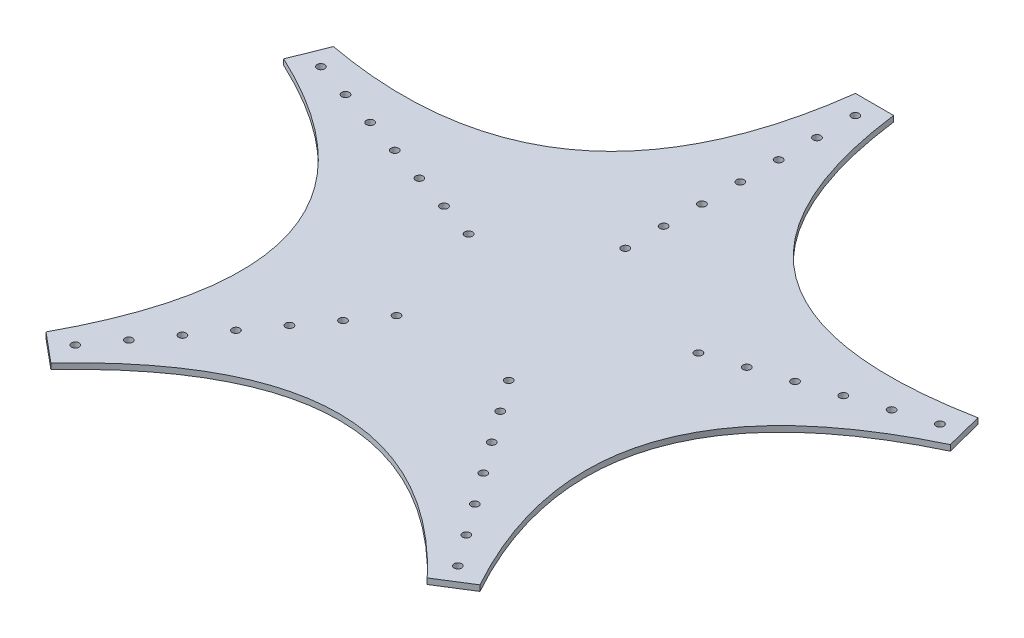
SolidWorks part; units mm, degrees
ref_plane "Front Plane" through (0, 0, 0) normal (0, 0, 1) x (1, 0, 0)
ref_plane "Top Plane" through (0, 0, 0) normal (0, 1, 0) x (1, 0, 0)
ref_plane "Right Plane" through (0, 0, 0) normal (1, 0, 0) x (0, 0, -1)
sketch "Sketch1" plane through (0, 0, 0) normal (0, 1, 0) x (1, 0, 0)
  line L0 (0, 0) -> (0, 50.8) construction
  line L1 (52.2614, 3.6272) -> (44.4123, 27.784)
  line L2 (12.7, 50.8244) -> (-12.7, 50.8244)
  line L3 (12.7, 50.8244) -> (12.7, 812.8244)
  line L4 (12.7, 812.8244) -> (-12.7, 812.8244)
  line L5 (-12.7, 50.8244) -> (-12.7, 812.8244)
  line L6 (52.2614, 3.6272) -> (776.9664, 239.0981)
  line L7 (776.9664, 239.0981) -> (769.1174, 263.255)
  line L8 (44.4123, 27.784) -> (769.1174, 263.255)
  line L9 (0, 0) -> (48.3137, 15.6981) construction
  line L10 (19.5993, -48.5827) -> (40.1483, -33.6529)
  line L11 (19.5993, -48.5827) -> (467.4917, -665.0536)
  line L12 (467.4917, -665.0536) -> (488.0407, -650.1239)
  line L13 (40.1483, -33.6529) -> (488.0407, -650.1239)
  line L14 (0, 0) -> (29.8595, -41.0981) construction
  line L15 (-40.1483, -33.6529) -> (-19.5993, -48.5827)
  line L16 (-40.1483, -33.6529) -> (-488.0407, -650.1239)
  line L17 (-488.0407, -650.1239) -> (-467.4917, -665.0536)
  line L18 (-19.5993, -48.5827) -> (-467.4917, -665.0536)
  line L19 (0, 0) -> (-29.8595, -41.0981) construction
  line L20 (-44.4123, 27.784) -> (-52.2614, 3.6272)
  line L21 (-44.4123, 27.784) -> (-769.1174, 263.255)
  line L22 (-769.1174, 263.255) -> (-776.9664, 239.0981)
  line L23 (-52.2614, 3.6272) -> (-776.9664, 239.0981)
  line L24 (0, 0) -> (-48.3137, 15.6981) construction
  circle A0 centre (0, 63.5244) radius 2.54
  circle A1 centre (0, 89.0462) radius 2.54
  circle A2 centre (0, 114.5681) radius 2.54
  circle A3 centre (0, 140.09) radius 2.54
  circle A4 centre (0, 165.6119) radius 2.54
  circle A5 centre (0, 191.1337) radius 2.54
  circle A6 centre (0, 216.6556) radius 2.54
  circle A7 centre (0, 242.1775) radius 2.54
  circle A8 centre (0, 267.6993) radius 2.54
  circle A9 centre (0, 293.2212) radius 2.54
  circle A10 centre (0, 318.7431) radius 2.54
  circle A11 centre (0, 344.2649) radius 2.54
  circle A12 centre (0, 369.7868) radius 2.54
  circle A13 centre (0, 395.3087) radius 2.54
  circle A14 centre (0, 420.8305) radius 2.54
  circle A15 centre (0, 446.3524) radius 2.54
  circle A16 centre (0, 471.8743) radius 2.54
  circle A17 centre (0, 497.3961) radius 2.54
  circle A18 centre (0, 522.918) radius 2.54
  circle A19 centre (0, 548.4399) radius 2.54
  circle A20 centre (0, 573.9618) radius 2.54
  circle A21 centre (0, 599.4836) radius 2.54
  circle A22 centre (0, 625.0055) radius 2.54
  circle A23 centre (0, 650.5274) radius 2.54
  circle A24 centre (0, 676.0492) radius 2.54
  circle A25 centre (0, 701.5711) radius 2.54
  circle A26 centre (0, 727.093) radius 2.54
  circle A27 centre (0, 752.6148) radius 2.54
  circle A28 centre (0, 778.1367) radius 2.54
  circle A29 centre (0, 803.6586) radius 2.54
  circle A30 centre (60.4153, 19.6301) radius 2.54
  circle A31 centre (84.688, 27.5168) radius 2.54
  circle A32 centre (108.9607, 35.4035) radius 2.54
  circle A33 centre (133.2335, 43.2902) radius 2.54
  circle A34 centre (157.5062, 51.1769) radius 2.54
  circle A35 centre (181.779, 59.0636) radius 2.54
  circle A36 centre (206.0517, 66.9503) radius 2.54
  circle A37 centre (230.3244, 74.837) radius 2.54
  circle A38 centre (254.5972, 82.7236) radius 2.54
  circle A39 centre (278.8699, 90.6103) radius 2.54
  circle A40 centre (303.1427, 98.497) radius 2.54
  circle A41 centre (327.4154, 106.3837) radius 2.54
  circle A42 centre (351.6881, 114.2704) radius 2.54
  circle A43 centre (375.9609, 122.1571) radius 2.54
  circle A44 centre (400.2336, 130.0438) radius 2.54
  circle A45 centre (424.5064, 137.9305) radius 2.54
  circle A46 centre (448.7791, 145.8172) radius 2.54
  circle A47 centre (473.0518, 153.7039) radius 2.54
  circle A48 centre (497.3246, 161.5906) radius 2.54
  circle A49 centre (521.5973, 169.4772) radius 2.54
  circle A50 centre (545.8701, 177.3639) radius 2.54
  circle A51 centre (570.1428, 185.2506) radius 2.54
  circle A52 centre (594.4155, 193.1373) radius 2.54
  circle A53 centre (618.6883, 201.024) radius 2.54
  circle A54 centre (642.961, 208.9107) radius 2.54
  circle A55 centre (667.2338, 216.7974) radius 2.54
  circle A56 centre (691.5065, 224.6841) radius 2.54
  circle A57 centre (715.7792, 232.5708) radius 2.54
  circle A58 centre (740.052, 240.4575) radius 2.54
  circle A59 centre (764.3247, 248.3442) radius 2.54
  circle A60 centre (37.3387, -51.3923) radius 2.54
  circle A61 centre (52.3401, -72.0399) radius 2.54
  circle A62 centre (67.3414, -92.6875) radius 2.54
  circle A63 centre (82.3428, -113.3352) radius 2.54
  circle A64 centre (97.3442, -133.9828) radius 2.54
  circle A65 centre (112.3456, -154.6304) radius 2.54
  circle A66 centre (127.347, -175.2781) radius 2.54
  circle A67 centre (142.3483, -195.9257) radius 2.54
  circle A68 centre (157.3497, -216.5733) radius 2.54
  circle A69 centre (172.3511, -237.2209) radius 2.54
  circle A70 centre (187.3525, -257.8686) radius 2.54
  circle A71 centre (202.3539, -278.5162) radius 2.54
  circle A72 centre (217.3552, -299.1638) radius 2.54
  circle A73 centre (232.3566, -319.8114) radius 2.54
  circle A74 centre (247.358, -340.4591) radius 2.54
  circle A75 centre (262.3594, -361.1067) radius 2.54
  circle A76 centre (277.3607, -381.7543) radius 2.54
  circle A77 centre (292.3621, -402.4019) radius 2.54
  circle A78 centre (307.3635, -423.0496) radius 2.54
  circle A79 centre (322.3649, -443.6972) radius 2.54
  circle A80 centre (337.3663, -464.3448) radius 2.54
  circle A81 centre (352.3676, -484.9924) radius 2.54
  circle A82 centre (367.369, -505.6401) radius 2.54
  circle A83 centre (382.3704, -526.2877) radius 2.54
  circle A84 centre (397.3718, -546.9353) radius 2.54
  circle A85 centre (412.3731, -567.5829) radius 2.54
  circle A86 centre (427.3745, -588.2306) radius 2.54
  circle A87 centre (442.3759, -608.8782) radius 2.54
  circle A88 centre (457.3773, -629.5258) radius 2.54
  circle A89 centre (472.3787, -650.1734) radius 2.54
  circle A90 centre (-37.3387, -51.3923) radius 2.54
  circle A91 centre (-52.3401, -72.0399) radius 2.54
  circle A92 centre (-67.3414, -92.6875) radius 2.54
  circle A93 centre (-82.3428, -113.3352) radius 2.54
  circle A94 centre (-97.3442, -133.9828) radius 2.54
  circle A95 centre (-112.3456, -154.6304) radius 2.54
  circle A96 centre (-127.347, -175.2781) radius 2.54
  circle A97 centre (-142.3483, -195.9257) radius 2.54
  circle A98 centre (-157.3497, -216.5733) radius 2.54
  circle A99 centre (-172.3511, -237.2209) radius 2.54
  circle A100 centre (-187.3525, -257.8686) radius 2.54
  circle A101 centre (-202.3539, -278.5162) radius 2.54
  circle A102 centre (-217.3552, -299.1638) radius 2.54
  circle A103 centre (-232.3566, -319.8114) radius 2.54
  circle A104 centre (-247.358, -340.4591) radius 2.54
  circle A105 centre (-262.3594, -361.1067) radius 2.54
  circle A106 centre (-277.3607, -381.7543) radius 2.54
  circle A107 centre (-292.3621, -402.4019) radius 2.54
  circle A108 centre (-307.3635, -423.0496) radius 2.54
  circle A109 centre (-322.3649, -443.6972) radius 2.54
  circle A110 centre (-337.3663, -464.3448) radius 2.54
  circle A111 centre (-352.3676, -484.9924) radius 2.54
  circle A112 centre (-367.369, -505.6401) radius 2.54
  circle A113 centre (-382.3704, -526.2877) radius 2.54
  circle A114 centre (-397.3718, -546.9353) radius 2.54
  circle A115 centre (-412.3731, -567.5829) radius 2.54
  circle A116 centre (-427.3745, -588.2306) radius 2.54
  circle A117 centre (-442.3759, -608.8782) radius 2.54
  circle A118 centre (-457.3773, -629.5258) radius 2.54
  circle A119 centre (-472.3787, -650.1734) radius 2.54
  circle A120 centre (-60.4153, 19.6301) radius 2.54
  circle A121 centre (-84.688, 27.5168) radius 2.54
  circle A122 centre (-108.9607, 35.4035) radius 2.54
  circle A123 centre (-133.2335, 43.2902) radius 2.54
  circle A124 centre (-157.5062, 51.1769) radius 2.54
  circle A125 centre (-181.779, 59.0636) radius 2.54
  circle A126 centre (-206.0517, 66.9503) radius 2.54
  circle A127 centre (-230.3244, 74.837) radius 2.54
  circle A128 centre (-254.5972, 82.7236) radius 2.54
  circle A129 centre (-278.8699, 90.6103) radius 2.54
  circle A130 centre (-303.1427, 98.497) radius 2.54
  circle A131 centre (-327.4154, 106.3837) radius 2.54
  circle A132 centre (-351.6881, 114.2704) radius 2.54
  circle A133 centre (-375.9609, 122.1571) radius 2.54
  circle A134 centre (-400.2336, 130.0438) radius 2.54
  circle A135 centre (-424.5064, 137.9305) radius 2.54
  circle A136 centre (-448.7791, 145.8172) radius 2.54
  circle A137 centre (-473.0518, 153.7039) radius 2.54
  circle A138 centre (-497.3246, 161.5906) radius 2.54
  circle A139 centre (-521.5973, 169.4772) radius 2.54
  circle A140 centre (-545.8701, 177.3639) radius 2.54
  circle A141 centre (-570.1428, 185.2506) radius 2.54
  circle A142 centre (-594.4155, 193.1373) radius 2.54
  circle A143 centre (-618.6883, 201.024) radius 2.54
  circle A144 centre (-642.961, 208.9107) radius 2.54
  circle A145 centre (-667.2338, 216.7974) radius 2.54
  circle A146 centre (-691.5065, 224.6841) radius 2.54
  circle A147 centre (-715.7792, 232.5708) radius 2.54
  circle A148 centre (-740.052, 240.4575) radius 2.54
  circle A149 centre (-764.3247, 248.3442) radius 2.54
  point P9 (112.3456, -154.6304)
  point P329 (0, 0)
  dimension "D5" = 5.08
  dimension "D6" = 12.7
  dimension "D7" = 12.7
  dimension "D1" = 50.8
  dimension "D2" = 762
  dimension "D3" = 25.4
  dimension "D4" = 12.7
  dimension "D8" = 30
  dimension "D9" = 5
sketch "Sketch2" plane through (0, 0, 0) normal (0, 1, 0) x (1, 0, 0)
  line L0 (-213.487, 82.7197) -> (-222.9511, 59.0876)
  line L1 (-44.4123, 27.784) -> (-769.1174, 263.255) construction
  line L2 (-52.2614, 3.6272) -> (-776.9664, 239.0981) construction
  line L4 (-40.1483, -33.6529) -> (-488.0407, -650.1239) construction
  line L5 (-144.6422, -177.4764) -> (-125.0914, -193.78)
  line L6 (-19.5993, -48.5827) -> (-467.4917, -665.0536) construction
  line L8 (19.5993, -48.5827) -> (467.4917, -665.0536) construction
  line L9 (124.0932, -192.4062) -> (145.6404, -178.8503)
  line L10 (40.1483, -33.6529) -> (488.0407, -650.1239) construction
  line L12 (52.2614, 3.6272) -> (776.9664, 239.0981) construction
  line L13 (221.336, 58.5629) -> (215.1021, 83.2445)
  line L14 (44.4123, 27.784) -> (769.1174, 263.255) construction
  line L16 (12.7, 50.8244) -> (12.7, 812.8244) construction
  line L17 (12.7, 229.4775) -> (-12.7, 229.4775)
  line L18 (-12.7, 50.8244) -> (-12.7, 812.8244) construction
  spline S0 degree 2 poles (-222.9511, 59.0876) (-58.2166, -17.9369) (-144.6422, -177.4764) knots 0 0 0 1 1 1
  spline S1 degree 2 poles (-125.0914, -193.78) (-0.9309, -60.9101) (124.0932, -192.4062) knots 0 0 0 1 1 1
  spline S2 degree 2 poles (145.6404, -178.8503) (57.6412, -19.7076) (221.336, 58.5629) knots 0 0 0 1 1 1
  spline S3 degree 2 poles (215.1021, 83.2445) (35.9905, 48.6982) (12.7, 229.4775) knots 0 0 0 1 1 1
  spline S4 degree 2 poles (-12.7, 229.4775) (-35.7071, 49.7533) (-213.487, 82.7197) knots 0 0 0 1 1 1
  point P40 (0, 0)
  dimension "D6" = 127
  dimension "D1" = 12.7
  dimension "D2" = 12.7
  dimension "D3" = 12.7
  dimension "D4" = 12.7
  dimension "D5" = 12.7
  dimension "D7" = 127
  dimension "D8" = 127
  dimension "D9" = 127
  dimension "D10" = 127
  dimension "D11" = 61.797
  dimension "D12" = 61.797
  dimension "D13" = 61.797
  dimension "D14" = 61.797
  dimension "D15" = 61.797
extrude "Boss-Extrude1" add sketch "Sketch2" along normal blind 3.81 contours L0 S0 L5 S1 L9 S2 L13 S3 L17 S4
extrude "Cut-Extrude2" cut sketch "Sketch1" along normal blind 3.81 contours A32 | A31 | A63 | A64 | A66 | A126 | A125 | A124 | A123 | A122 | A121 | A120 | A6 | A5 | A4 | A3 | A2 | A1 | A0 | A36 | A35 | A34 | A33 | A60 | A61 | A62 | A65 | A96 | A95 | A94 | A93 | A92 | A91 | A90 region at (84.688, 0, -27.5168) region at (108.9607, 0, -35.4035) region at (82.3428, 0, 113.3352) region at (97.3442, 0, 133.9828) region at (127.347, 0, 175.2781)
